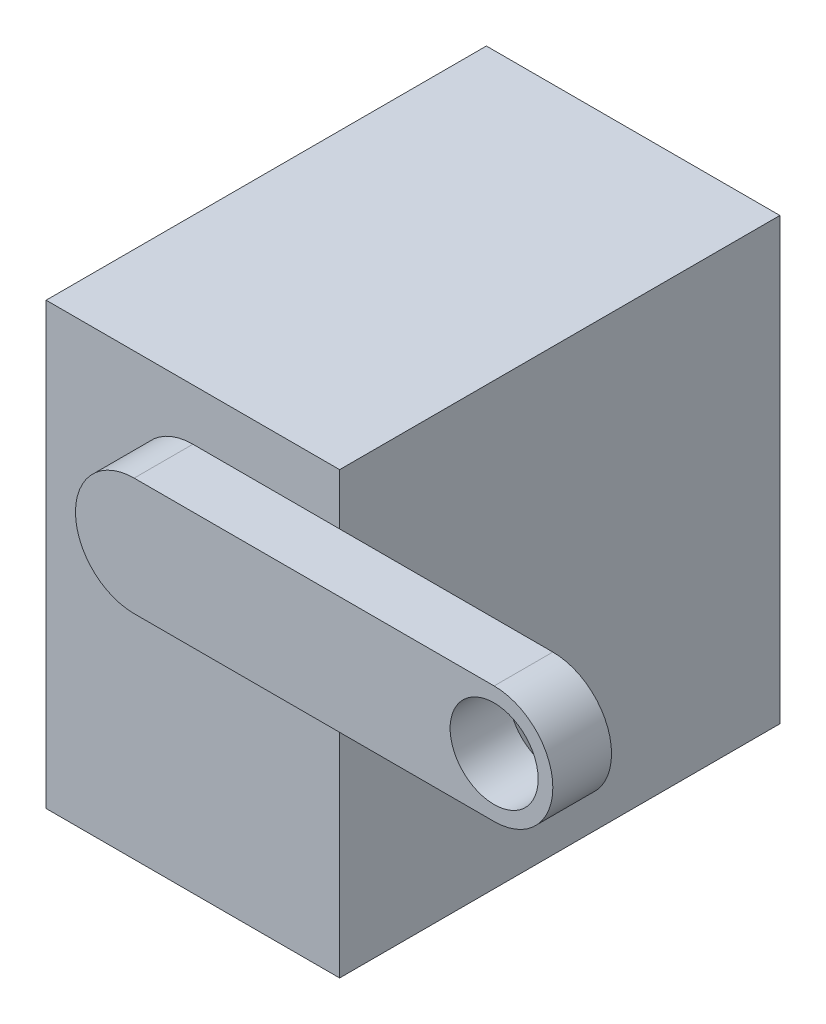
SolidWorks part; units mm, degrees
ref_plane "Plan de face" through (0, 0, 0) normal (0, 0, 1) x (1, 0, 0)
ref_plane "Plan de dessus" through (0, 0, 0) normal (0, 1, 0) x (1, 0, 0)
ref_plane "Plan de droite" through (0, 0, 0) normal (1, 0, 0) x (0, 0, -1)
sketch "Esquisse1" plane through (0, 0, 0) normal (0, 0, 1) x (1, 0, 0)
  line L1 (-10, -15) -> (10, -15)
  line L2 (-10, -15) -> (-10, 15)
  line L3 (-10, 15) -> (10, 15)
  line L4 (10, -15) -> (10, 15)
  line L5 (-10, -15) -> (10, 15) construction
  line L6 (-10, 15) -> (10, -15) construction
  point P0 (0, 0)
  dimension "D1" = 20
  dimension "D2" = 30
extrude "Boss.-Extru.1" add sketch "Esquisse1" along normal blind 30
sketch "Esquisse2" plane through (0, 0, 30) normal (0, 0, 1) x (1, 0, 0)
  line L0 (0, 0) -> (-10, 0) construction
  line L1 (-10, 15) -> (-10, -15) construction
  line L2 (-10, 0) -> (10, 15) construction
  line L3 (0, 11.5) -> (24.5287, 11.5)
  line L4 (0, 3.5) -> (24.5287, 3.5)
  arc A0 (0, 11.5) -> (0, 3.5) centre (0, 7.5) ccw
  arc A1 (24.5287, 3.5) -> (24.5287, 11.5) centre (24.5287, 7.5) ccw
  circle A2 centre (24.5287, 7.5) radius 3
  dimension "D1" = 8
  dimension "D2" = 1
extrude "Boss.-Extru.2" add sketch "Esquisse2" along normal blind 4
